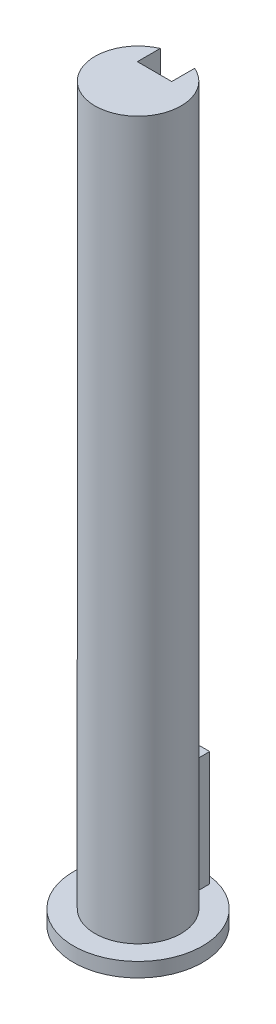
SolidWorks part; units mm, degrees
ref_plane "정면" through (0, 0, 0) normal (0, 0, 1) x (1, 0, 0)
ref_plane "윗면" through (0, 0, 0) normal (0, 1, 0) x (1, 0, 0)
ref_plane "우측면" through (0, 0, 0) normal (1, 0, 0) x (0, 0, -1)
sketch "스케치1" plane through (0, 0, 0) normal (0, 1, 0) x (1, 0, 0)
  line L0 (-1, 2.8284) -> (-1, 4)
  line L1 (-1, 4) -> (1, 4)
  line L2 (1, 4) -> (1, 2.8284)
  circle A0 centre (0, 0) radius 3
  dimension "D1" = 6
  dimension "D2" = 4
  dimension "D3" = 1
  dimension "D4" = 2
extrude "보스-돌출2" add sketch "스케치1" along normal blind 50 contours A0 region at (0, 0, 0)
extrude "보스-돌출3" add sketch "스케치1<3>" along normal blind 8 contours A0 L2 L1 L0 region at (0, 0, -3.4705)
sketch "스케치1<3>" plane through (0, 0, 0) normal (0, 1, 0) x (1, 0, 0) same geometry as "스케치1"
sketch "스케치2" plane through (0, 50, 0) normal (0, 1, 0) x (1, 0, 0)
  line L5 (-1.2, 1.1495) -> (1.2, 1.1495)
  line L6 (1.2, 1.1495) -> (1.2, 2.7495)
  line L7 (-1.2, 1.1495) -> (-1.2, 2.7495)
  line L8 (0, 0) -> (0, 1.1495) construction
  line L9 (-1.2, 2.7495) -> (0, 4.828)
  line L10 (0, 4.828) -> (1.2, 2.7495)
  circle A0 centre (0, 0) radius 3 construction
  dimension "D1" = 1.6
  dimension "D5" = 2.4
  dimension "D6" = 60
  dimension "D7" = 150
extrude "컷-돌출1" cut sketch "스케치2" against normal blind 26
sketch "스케치3" plane through (0, 0, 0) normal (0, -1, 0) x (1, 0, 0)
  circle A0 centre (0, 0) radius 4.5
  dimension "D1" = 9
extrude "보스-돌출4" add sketch "스케치3" along normal blind 1
